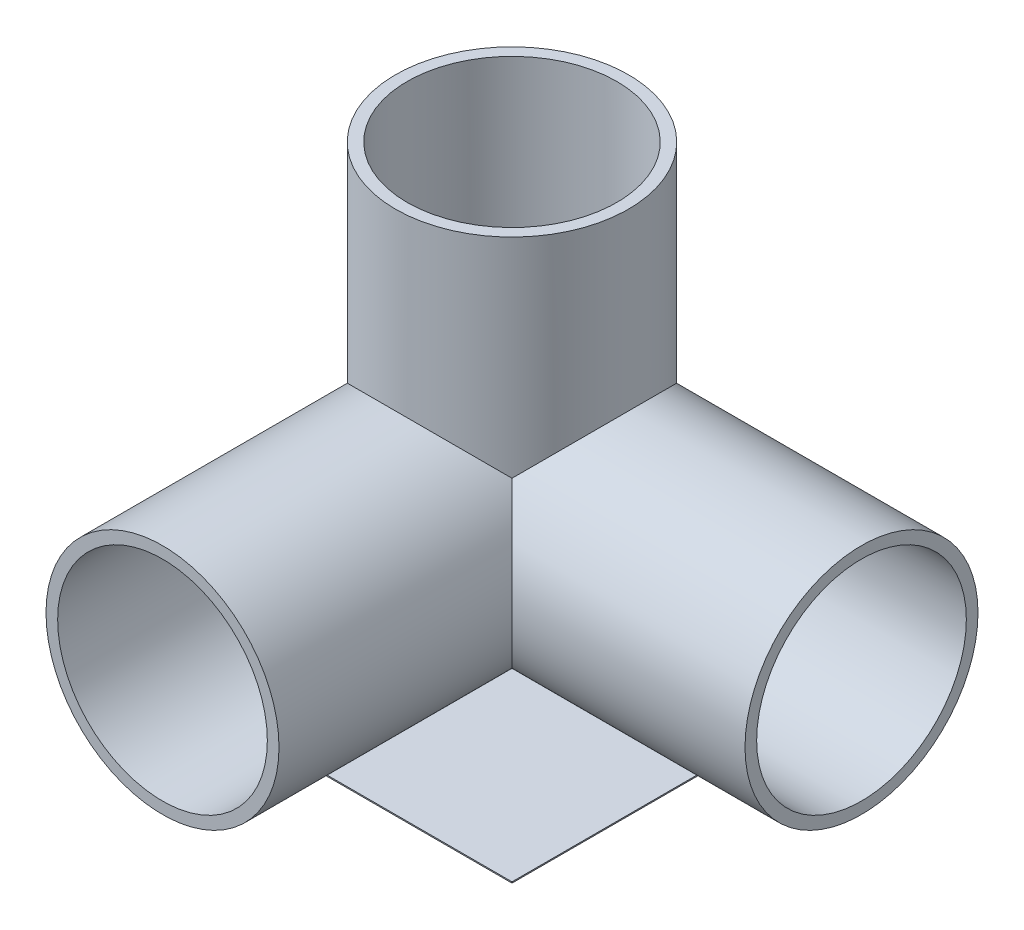
SolidWorks part; units mm, degrees
ref_plane "前视基准面" through (0, 0, 0) normal (0, 0, 1) x (1, 0, 0)
ref_plane "上视基准面" through (0, 0, 0) normal (0, 1, 0) x (1, 0, 0)
ref_plane "右视基准面" through (0, 0, 0) normal (1, 0, 0) x (0, 0, -1)
sketch "草图9" plane through (0, 0, 0) normal (0, 1, 0) x (1, 0, 0)
  line L0 (-96.4906, -33.1714) -> (-96.4906, -3.1714)
  line L1 (-96.4906, -3.1714) -> (-66.4906, -3.1714)
  dimension "D1" = 30
  dimension "D2" = 30
ref_plane "基准面4" through (0, 0, 33.1714) normal (0, 0, 1) x (1, 0, 0)
ref_plane "基准面5" through (-66.4906, 0, 0) normal (1, 0, 0) x (0, 0, -1)
sweep "扫描1" add path "草图9" circular profile diameter 20 parameters "D3"=20
ref_plane "基准面6" through (0, 25, 0) normal (0, 1, 0) x (1, 0, 0)
sketch "草图19" plane through (0, 25, 0) normal (0, 1, 0) x (1, 0, 0)
  line L0 (-106.4906, 6.8286) -> (-86.4906, -13.1714) construction
  circle A0 centre (-96.4906, -3.1714) radius 10
extrude "凸台-拉伸9" add sketch "草图19" against normal up to next
sketch "草图20" plane through (0, 0, 33.1714) normal (0, 0, 1) x (1, 0, 0)
  circle A2 centre (-96.4906, 0) radius 9
  dimension "D1" = 18
extrude "切除-拉伸1" cut sketch "草图20" against normal blind 28
sketch "草图21" plane through (-66.4906, 0, 0) normal (1, 0, 0) x (0, 0, -1)
  circle A0 centre (-3.1714, 0) radius 9
  dimension "D1" = 18
extrude "切除-拉伸2" cut sketch "草图21" against normal blind 28
sketch "草图22" plane through (0, 25, 0) normal (0, 1, 0) x (1, 0, 0)
  circle A0 centre (-96.4906, -3.1714) radius 9
  dimension "D1" = 18
extrude "切除-拉伸4" cut sketch "草图22" against normal blind 28
sketch "草图23" plane through (0, 0, 0) normal (0, 1, 0) x (1, 0, 0)
  line L0 (-76.4906, 6.8286) -> (-76.4906, -23.1714)
  line L1 (-106.4906, 6.8286) -> (-76.4906, 6.8286)
  line L2 (-106.4906, 6.8286) -> (-106.4906, -23.1714)
  line L5 (-76.4906, -23.1714) -> (-106.4906, -23.1714)
  dimension "D1" = 30
  dimension "D2" = 30
extrude "凸台-拉伸10" add sketch "草图23" against normal blind 0.1 from offset 10 separate body offset against normal yes
